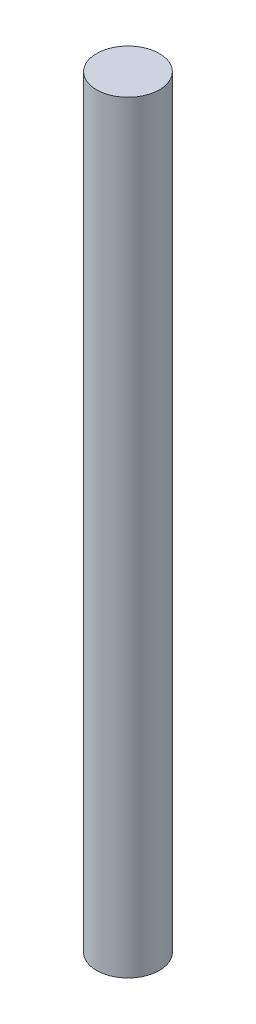
SolidWorks part; units mm, degrees
ref_plane "Front Plane" through (0, 0, 0) normal (0, 0, 1) x (1, 0, 0)
ref_plane "Top Plane" through (0, 0, 0) normal (0, 1, 0) x (1, 0, 0)
ref_plane "Right Plane" through (0, 0, 0) normal (1, 0, 0) x (0, 0, -1)
sketch "Elevation Bar" plane through (0, 0, 0) normal (0, 1, 0) x (1, 0, 0)
  circle A0 centre (0, 0) radius 30.226
  dimension "D1" = 60.452
extrude "Elevation Bar Part" add sketch "Elevation Bar" along normal blind 734.06
sketch "Sketch2" plane through (0, 0, 0) normal (0, 0, 1) x (1, 0, 0)
  line L0 (0, 0) -> (172.1794, 0) construction
  line L1 (-30.226, 0) -> (-30.226, 734.06) construction
  line L2 (-30.226, 734.06) -> (30.226, 734.06) construction
  line L3 (30.226, 734.06) -> (30.226, 0) construction
  line L4 (30.226, 0) -> (30.226, 734.06) construction
  line L5 (636.651, 40.7185) -> (27.051, 40.7185) construction
  line L6 (636.651, 53.4185) -> (27.051, 53.4185)
  line L7 (636.651, 53.4185) -> (636.651, 28.0185)
  line L8 (636.651, 28.0185) -> (27.051, 28.0185)
  line L9 (27.051, 53.4185) -> (27.051, 28.0185)
  circle A0 centre (576.5632, 40.7185) radius 41.275 construction
  circle A1 centre (87.1388, 40.7185) radius 41.275 construction
  circle A2 centre (331.851, 40.7185) radius 41.275 construction
  point P24 (331.851, 40.7185)
  point P25 (0, 0)
  point P26 (0, 0)
  point P27 (27.051, 40.7185)
  dimension "D2" = 82.55
  dimension "D1" = 609.6
  dimension "D3" = 25.4
  dimension "D4" = 244.7122
  dimension "D5" = 244.7122
sketch "Sketch4" plane through (0, 0, 0) normal (0, 0, 1) x (1, 0, 0)
  line L0 (-30.226, 164.5435) -> (-30.226, 81.9935) construction
  line L1 (52.451, 81.9935) -> (27.051, 81.9935) construction
  line L2 (-30.226, 0) -> (-30.226, 734.06) construction
  line L3 (30.226, 734.06) -> (30.226, 0) construction
  line L4 (-30.226, 164.5435) -> (30.226, 81.9935) construction
  line L5 (30.226, 81.9935) -> (-30.226, 81.9935) construction
  line L6 (27.051, 81.9935) -> (-30.226, 164.5435) construction
  line L7 (27.051, 81.9935) -> (27.051, 40.7185) construction
  line L11 (636.651, 53.4185) -> (27.051, 53.4185) construction
  circle A0 centre (52.451, 81.9935) radius 20.6375
  circle A1 centre (52.451, 81.9935) radius 25.4
  circle A2 centre (52.451, 81.9935) radius 22.225 construction
  circle A3 centre (-46.488, 164.5435) radius 16.262
  dimension "D1" = 50.8
  dimension "D2" = 41.275
  dimension "D3" = 1.5875
  dimension "D4" = 3.175
  dimension "D5" = 82.55
  dimension "D6" = 53.784
  dimension "D7" = 55.245
equation "\"D5@Sketch2\"=\"D4@Sketch2\""
